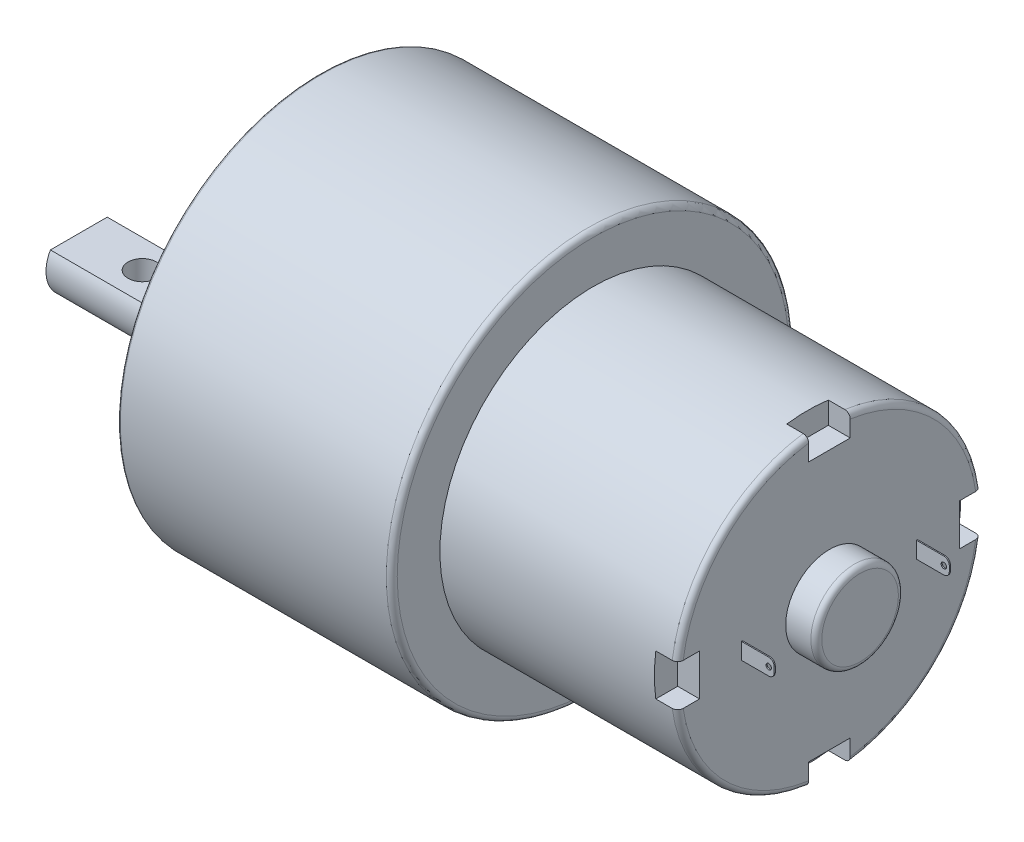
SolidWorks part; units mm, degrees
ref_plane "Front Plane" through (0, 0, 0) normal (0, 0, 1) x (1, 0, 0)
ref_plane "Top Plane" through (0, 0, 0) normal (0, 1, 0) x (1, 0, 0)
ref_plane "Right Plane" through (0, 0, 0) normal (1, 0, 0) x (0, 0, -1)
sketch "Sketch1" plane through (0, 0, 0) normal (1, 0, 0) x (0, 0, -1)
  circle A0 centre (0, 0) radius 18.4
  dimension "D1" = 36.8
extrude "Boss-Extrude1" add sketch "Sketch1" along normal blind 25
sketch "Sketch2" plane through (0, 0, 0) normal (-1, 0, 0) x (0, 0, 1)
  line L0 (0, 0) -> (50000, 0) construction
  circle A1 centre (0, 0) radius 15.5 construction
  circle A2 centre (15.5, 0) radius 1.5
  circle A3 centre (7.75, -13.4234) radius 1.5
  circle A4 centre (-7.75, -13.4234) radius 1.5
  circle A5 centre (-15.5, 0) radius 1.5
  circle A6 centre (-7.75, 13.4234) radius 1.5
  circle A7 centre (7.75, 13.4234) radius 1.5
  point P19 (0, 0)
  dimension "D1" = 6
  dimension "D2" = 31
  dimension "D3" = 3
extrude "Cut-Extrude1" cut sketch "Sketch2" against normal blind 5
sketch "Sketch4" plane through (0, 0, 0) normal (-1, 0, 0) x (0, 0, 1)
  line L0 (-15.5, 0) -> (15.5, 0) construction
  line L1 (0, 0) -> (0, -18.4) construction
  line L2 (7.75, -13.4234) -> (-7.75, -13.4234) construction
  line L3 (0, -12.8) -> (0, -0.8) construction
  line L4 (0, -13.4234) -> (0, -12.8) construction
  line L5 (-6, -6.8) -> (6, -6.8) construction
  circle A0 centre (0, -6.8) radius 6
  circle A1 centre (0, 0) radius 18.4 construction
  point P21 (0, -6.8)
  point P24 (0, -6.8)
  dimension "D1" = 17.6
  dimension "D2" = 12
extrude "Boss-Extrude2" add sketch "Sketch4" along normal blind 6.5
sketch "Sketch5" plane through (-6.5, 0, 0) normal (-1, 0, 0) x (0, 0, 1)
  arc A0 (-1.354, -4.1229) -> (1.354, -4.1229) centre (0, -6.8) ccw
  circle A1 centre (0, -6.8) radius 6 construction
  arc A2 (-1.354, -4.1229) -> (1.354, -4.1229) centre (0, -6.8) cw
  dimension "D1" = 3
extrude "Boss-Extrude3" add sketch "Sketch5" along normal blind 15.5
sketch "Sketch7" plane through (0, 0, 0) normal (-1, 0, 0) x (0, 0, 1)
  arc A0 (7.8302, -9.0933) -> (-7.8302, -9.0933) centre (0, 0) ccw
  arc A2 (7.8302, -9.0933) -> (-7.8302, -9.0933) centre (0, -6.4952) ccw
extrude "Cut-Extrude2" cut sketch "Sketch7" against normal blind 0.3
sketch "Sketch8" plane through (25, 0, 0) normal (1, 0, 0) x (0, 0, -1)
  circle A0 centre (0, 0) radius 14
extrude "Boss-Extrude5" add sketch "Sketch8" along normal blind 21.6
sketch "Sketch9" plane through (46.6, 0, 0) normal (1, 0, 0) x (0, 0, -1)
  line L0 (13.5, 0) -> (14, 0) construction
  circle A0 centre (0, 0) radius 13.5
  circle A1 centre (0, 0) radius 14 construction
extrude "Cut-Extrude3" [suppressed] cut sketch "Sketch9" against normal blind 1
sketch "Sketch10" plane through (46.6, 0, 0) normal (1, 0, 0) x (0, 0, -1)
  line L0 (0, 0) -> (9.8995, 9.8995) construction
  line L1 (8.6153, 10.0295) -> (9.3403, 10.7545)
  line L2 (9.3403, 10.7545) -> (10.7545, 9.3403)
  line L3 (10.7545, 9.3403) -> (10.0295, 8.6153)
  line L4 (10.0295, 8.6153) -> (9.3224, 9.3224)
  line L5 (9.3224, 9.3224) -> (8.6153, 10.0295)
  line L6 (9.3224, -9.3224) -> (10.0295, -8.6153)
  line L7 (10.0295, -8.6153) -> (10.7545, -9.3403)
  line L8 (10.7545, -9.3403) -> (9.3403, -10.7545)
  line L9 (9.3403, -10.7545) -> (8.6153, -10.0295)
  line L10 (8.6153, -10.0295) -> (9.3224, -9.3224)
  line L11 (-9.3224, -9.3224) -> (-8.6153, -10.0295)
  line L12 (-8.6153, -10.0295) -> (-9.3403, -10.7545)
  line L13 (-9.3403, -10.7545) -> (-10.7545, -9.3403)
  line L14 (-10.7545, -9.3403) -> (-10.0295, -8.6153)
  line L15 (-10.0295, -8.6153) -> (-9.3224, -9.3224)
  line L16 (-9.3224, 9.3224) -> (-10.0295, 8.6153)
  line L17 (-10.0295, 8.6153) -> (-10.7545, 9.3403)
  line L18 (-10.7545, 9.3403) -> (-9.3403, 10.7545)
  line L19 (-9.3403, 10.7545) -> (-8.6153, 10.0295)
  line L20 (-8.6153, 10.0295) -> (-9.3224, 9.3224)
  circle A0 centre (0, 0) radius 14 construction
  point P28 (0, 0)
  dimension "D1" = 4
extrude "Cut-Extrude4" [suppressed] cut sketch "Sketch10" against normal up to surface (1 mm away)
sketch "Sketch11" [suppressed] plane through (45.6, 0, 0) normal (1, 0, 0) x (0, 0, -1)
  circle A0 centre (0, 0) radius 10
extrude "Boss-Extrude6" [suppressed] add sketch "Sketch11" along normal blind 0.5
sketch "Sketch12" [suppressed] plane through (46.1, 0, 0) normal (1, 0, 0) x (0, 0, -1)
  circle A0 centre (0, 0) radius 5
extrude "Boss-Extrude7" [suppressed] add sketch "Sketch12" along normal blind 3
sketch "Sketch13" [suppressed] plane through (49.1, 0, 0) normal (1, 0, 0) x (0, 0, -1)
  circle A0 centre (0, 0) radius 3
extrude "Cut-Extrude5" [suppressed] cut sketch "Sketch13" against normal blind 0.5
sketch "Sketch15" [suppressed] plane through (48.6, 0, 0) normal (1, 0, 0) x (0, 0, -1)
  circle A0 centre (0, 0) radius 1.25
extrude "Boss-Extrude8" [suppressed] add sketch "Sketch15" along normal blind 2.5
sketch "Sketch16" [suppressed] plane through (45.6, 0, 0) normal (1, 0, 0) x (0, 0, -1)
  line L0 (-13.5, 0) -> (13.5, 0) construction
  line L1 (0, 0) -> (0, 10) construction
  line L2 (12.25, 1.5) -> (12.75, 1.5)
  line L3 (12.25, 1.5) -> (12.25, -1.5)
  line L4 (12.25, -1.5) -> (12.75, -1.5)
  line L5 (12.75, 1.5) -> (12.75, -1.5)
  line L6 (12.25, 1.5) -> (12.75, -1.5) construction
  line L7 (12.25, -1.5) -> (12.75, 1.5) construction
  line L8 (-12.25, -1.5) -> (-12.75, 1.5) construction
  line L9 (-12.25, 1.5) -> (-12.75, -1.5) construction
  line L10 (-12.75, 1.5) -> (-12.75, -1.5)
  line L11 (-12.25, -1.5) -> (-12.75, -1.5)
  line L12 (-12.25, 1.5) -> (-12.25, -1.5)
  line L13 (-12.25, 1.5) -> (-12.75, 1.5)
  arc A1 (10.2268, -8.8126) -> (10.2268, 8.8126) centre (0, 0) ccw construction
  circle A2 centre (0, 0) radius 10 construction
  circle A4 centre (0, 0) radius 10 construction
  point P6 (0, 0)
  point P10 (12.5, 0)
  point P22 (-12.5, 0)
  dimension "D1" = 0.75
  dimension "D2" = 0.5
  dimension "D3" = 3
extrude "Boss-Extrude9" [suppressed] add sketch "Sketch16" along normal blind 7
ref_plane "Plane1" through (28, 0, 0) normal (1, 0, 0) x (0, 0, -1)
sketch "Sketch17" plane through (28, 0, 0) normal (1, 0, 0) x (0, 0, -1)
  line L0 (-1.5514, 15.0201) -> (-1.4486, 14.0254)
  line L1 (1.4486, 14.0254) -> (1.5514, 15.0201)
  line L2 (-1.5, 14.5227) -> (1.5, 14.5227) construction
  line L3 (0, 14) -> (0, 14.1) construction
  arc A0 (-1.4486, 14.0254) -> (1.4486, 14.0254) centre (0, 0) ccw
  arc A1 (-1.5514, 15.0201) -> (1.5514, 15.0201) centre (0, 0) ccw
  circle A2 centre (0, 0) radius 14 construction
extrude "Boss-Extrude10" [suppressed] add sketch "Sketch17" along normal blind 21 separate body
fillet "Fillet1" [suppressed] radius 2
fillet "Fillet2" [suppressed] radius 0.5
fillet "Fillet3" radius 0.2 8 edges at (0, 0, -18.4) (-6.5, -6.8, 6) (0, -13.4234, 9.25) (0, 0, 17) (0, -13.4234, -6.25) (0, 0, -14) (0, 13.4234, -6.25) (0, 13.4234, 9.25)
fillet "Fillet4" [suppressed] radius 0.5
fillet "Fillet5" [suppressed] radius 1
fillet "Fillet8" [suppressed] radius 0.1
fillet "Fillet9" [suppressed] radius 0.2
fillet "Fillet11" [suppressed] type full round
fillet "Fillet12" [suppressed] type full round
sketch "Sketch19" [suppressed] plane through (0, 0, 12.75) normal (0, 0, 1) x (1, 0, 0)
  circle A0 centre (51.1, 0) radius 0.5
  dimension "D1" = 1
extrude "Cut-Extrude6" [suppressed] cut sketch "Sketch19" against normal blind 1
sketch "Sketch20" [suppressed] plane through (0, 0, -12.75) normal (0, 0, -1) x (-1, 0, 0)
  circle A0 centre (-51.1, 0) radius 0.5
  dimension "D1" = 1
extrude "Cut-Extrude7" [suppressed] cut sketch "Sketch20" against normal blind 1
sketch "Sketch21" plane through (0, 0, 0) normal (0, 1, 0) x (1, 0, 0)
  line L0 (-22, 0) -> (-11.5056, 0) construction
  line L2 (-22, 3) -> (-22, -3) construction
  circle A0 centre (-16.2, 0) radius 1.3
  dimension "D1" = 2.6
  dimension "D2" = 5.8
extrude "Cut-Extrude8" cut sketch "Sketch21" against normal mid plane 20
sketch "Sketch23" plane through (46.6, 0, 0) normal (1, 0, 0) x (0, 0, -1)
  line L0 (-14, 0) -> (14, 0) construction
  line L1 (0, -14) -> (0, 14) construction
  line L2 (-1.9, 13.8705) -> (-1.9, 11.8705)
  line L3 (-1.9, 11.8705) -> (1.9, 11.8705)
  line L4 (1.9, 11.8705) -> (1.9, 13.8705)
  line L5 (13.8705, 1.9) -> (11.8705, 1.9)
  line L6 (11.8705, 1.9) -> (11.8705, -1.9)
  line L7 (11.8705, -1.9) -> (13.8705, -1.9)
  line L8 (1.9, -13.8705) -> (1.9, -11.8705)
  line L9 (1.9, -11.8705) -> (-1.9, -11.8705)
  line L10 (-1.9, -11.8705) -> (-1.9, -13.8705)
  line L11 (-13.8705, -1.9) -> (-11.8705, -1.9)
  line L12 (-11.8705, -1.9) -> (-11.8705, 1.9)
  line L13 (-11.8705, 1.9) -> (-13.8705, 1.9)
  arc A0 (-1.9, -13.8705) -> (1.9, -13.8705) centre (0, 0) ccw
  circle A1 centre (0, 0) radius 14
  arc A2 (-13.8705, 1.9) -> (-13.8705, -1.9) centre (0, 0) ccw
  arc A3 (13.8705, -1.9) -> (13.8705, 1.9) centre (0, 0) ccw
  arc A4 (1.9, 13.8705) -> (-1.9, 13.8705) centre (0, 0) ccw
  point P6 (0, 0)
  point P9 (0, 0)
  point P28 (0, 0)
  dimension "D2" = 3.8
  dimension "D3" = 2
  dimension "D1" = 0
extrude "Cut-Extrude10" cut sketch "Sketch23" against normal blind 2
sketch "Sketch24" plane through (46.6, 0, 0) normal (1, 0, 0) x (0, 0, -1)
  circle A0 centre (0, 0) radius 4
  dimension "D1" = 8
extrude "Boss-Extrude11" add sketch "Sketch24" along normal blind 2.8
sketch "Sketch25" plane through (46.6, 0, 0) normal (1, 0, 0) x (0, 0, -1)
  line L0 (0, 0) -> (14, 0) construction
  line L1 (0, 0) -> (0, 6.9835) construction
  line L2 (7.95, -0.75) -> (8.05, -0.75)
  line L3 (7.95, -0.75) -> (7.95, 0.75)
  line L4 (7.95, 0.75) -> (8.05, 0.75)
  line L5 (8.05, -0.75) -> (8.05, 0.75)
  line L6 (7.95, -0.75) -> (8.05, 0.75) construction
  line L7 (7.95, 0.75) -> (8.05, -0.75) construction
  line L8 (-7.95, 0.75) -> (-8.05, -0.75) construction
  line L9 (-7.95, -0.75) -> (-8.05, 0.75) construction
  line L10 (-8.05, -0.75) -> (-8.05, 0.75)
  line L11 (-7.95, 0.75) -> (-8.05, 0.75)
  line L12 (-7.95, -0.75) -> (-7.95, 0.75)
  line L13 (-7.95, -0.75) -> (-8.05, -0.75)
  circle A0 centre (0, 0) radius 14 construction
  point P6 (8, 0)
  point P16 (-8, 0)
  dimension "D1" = 0.1
  dimension "D2" = 1.5
  dimension "D3" = 8
extrude "Boss-Extrude12" add sketch "Sketch25" along normal blind 3
fillet "Fillet13" radius 0.5 4 edges at (49.6, 0.75, -8) (49.6, -0.75, -8) (49.6, 0.75, 8) (49.6, -0.75, 8)
sketch "Sketch26" plane through (0, 0, 8.05) normal (0, 0, 1) x (1, 0, 0)
  line L0 (49.6, 0.25) -> (49.6, -0.25) construction
  line L1 (49.1, 0.75) -> (46.6, 0.75) construction
  circle A0 centre (49.1, 0) radius 0.25
  dimension "D1" = 0.5
  dimension "D2" = 0.5
  dimension "D3" = 0.75
extrude "Cut-Extrude11" cut sketch "Sketch26" against normal blind 2
mirror "Mirror1" about plane through (0, 0, 0) normal (0, 0, 1) of "Cut-Extrude11"
fillet "Fillet14" radius 0.5 1 edges at (49.4, 0, -4)
fillet "Fillet15" radius 0.5 4 edges at (46.6, -9.8995, -9.8995) (46.6, -9.8995, 9.8995) (46.6, 9.8995, -9.8995) (46.6, 9.8995, 9.8995)
fillet "Fillet16" radius 0.5 1 edges at (25, 0, -18.4)
sketch "Sketch27" plane through (-22, 0, 0) normal (-1, 0, 0) x (0, 0, 1)
  line L0 (-2.5981, -5.3) -> (2.5981, -5.3)
  circle A0 centre (0, -6.8) radius 3 construction
  arc A1 (2.5981, -5.3) -> (-2.5981, -5.3) centre (0, -6.8) ccw
  point P5 (0, -5.3)
  dimension "D1" = 1.5
extrude "Cut-Extrude12" cut sketch "Sketch27" against normal blind 14
ref_axis "Axis1" through (-24.2515, -6.8, 0) along (1, 0, 0)
